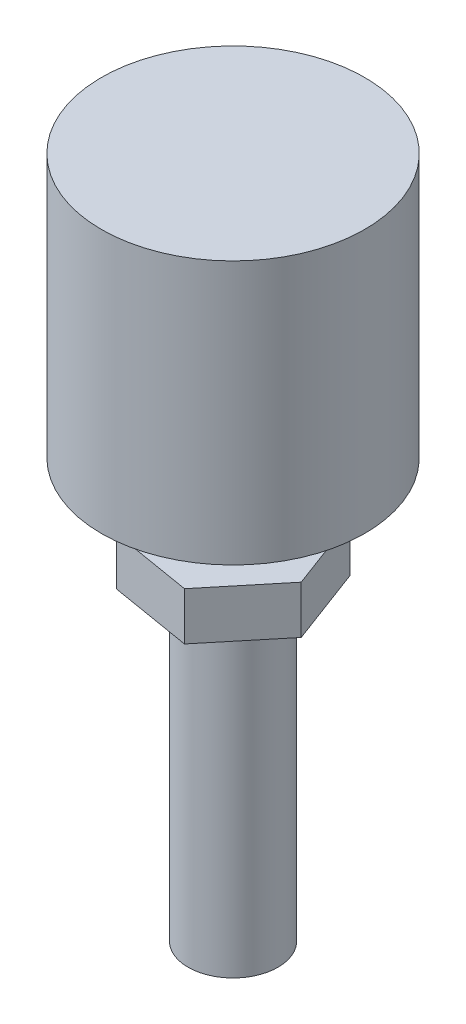
SolidWorks part; units mm, degrees
ref_plane "Front Plane" through (0, 0, 0) normal (0, 0, 1) x (1, 0, 0)
ref_plane "Top Plane" through (0, 0, 0) normal (0, 1, 0) x (1, 0, 0)
ref_plane "Right Plane" through (0, 0, 0) normal (1, 0, 0) x (0, 0, -1)
sketch "Sketch1" plane through (0, 0, 0) normal (0, 1, 0) x (1, 0, 0)
  circle A0 centre (0, 0) radius 11
  dimension "D1" = 22
extrude "Boss-Extrude1" add sketch "Sketch1" along normal blind 22
sketch "Sketch2" plane through (0, 0, 0) normal (0, -1, 0) x (1, 0, 0)
  line L1 (6.8339, 1.139) -> (2.4306, 6.4879)
  line L2 (2.4306, 6.4879) -> (-4.4034, 5.3489)
  line L3 (-4.4034, 5.3489) -> (-6.8339, -1.139)
  line L4 (-6.8339, -1.139) -> (-2.4306, -6.4879)
  line L5 (-2.4306, -6.4879) -> (4.4034, -5.3489)
  line L6 (4.4034, -5.3489) -> (6.8339, 1.139)
  circle A0 centre (0, 0) radius 6 construction
  dimension "D1" = 12
extrude "Boss-Extrude2" add sketch "Sketch2" along normal blind 4 from offset 5.03
sketch "Sketch3" plane through (0, -9.03, 0) normal (0, -1, 0) x (1, 0, 0)
  circle A0 centre (0, 0) radius 3.7586
extrude "Boss-Extrude3" add sketch "Sketch3" along normal blind 35 from surface starting at face at (0, 0, 11)
thread "Thread1" pitch 1 method cut profile "Thread Profile2" start angle 0, offset 0, length 10, pitch 1, diameter 7.5171
ref_plane "Plane2" through (-3.7586, 0, 0) normal (0, 0, 1) x (-1, 0, 0)
sketch "Thread Profile2" plane through (-3.7586, 0, 0) normal (0, 0, 1) x (-1, 0, 0)
  line L0 (0, 0) -> (0, 1) construction
  line L11 (0, 0) -> (0, 0.875)
  line L12 (0, 0.875) -> (-0.5413, 0.5625)
  line L13 (-0.5413, 0.5625) -> (-0.5413, 0.3125)
  line L15 (-0.5413, 0.3125) -> (0, 0)
  line L17 (-0.5413, 0.4375) -> (0, 0.4375) construction
  point P2 (0, 0)
  dimension "Pitch" = 1
  dimension "Profile_Angle" = 60
  dimension "Profile_Land" = 0.25
  dimension "Profile_Height" = 0.5413
